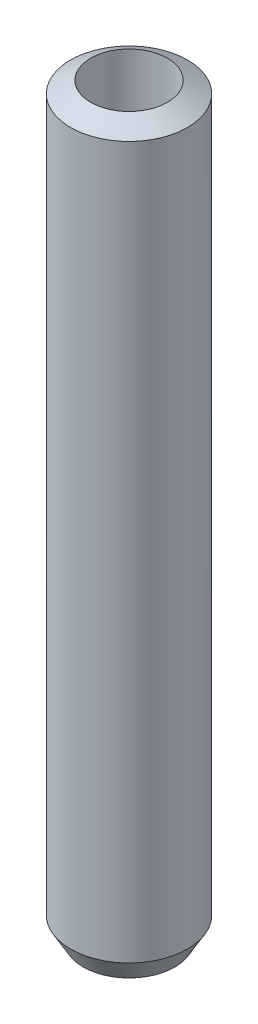
SolidWorks part; units mm, degrees
ref_plane "Front Plane" through (0, 0, 0) normal (0, 0, 1) x (1, 0, 0)
ref_plane "Top Plane" through (0, 0, 0) normal (0, 1, 0) x (1, 0, 0)
ref_plane "Right Plane" through (0, 0, 0) normal (1, 0, 0) x (0, 0, -1)
sketch "Sketch1" plane through (0, 0, 0) normal (0, 1, 0) x (1, 0, 0)
  circle A0 centre (0, 0) radius 17.5
  dimension "SHAFT_OD" = 35
extrude "Boss-Extrude1" add sketch "Sketch1" along normal blind 223.173
sketch "Sketch2" plane through (0, 0, 0) normal (0, 1, 0) x (1, 0, 0)
  circle A0 centre (0, 0) radius 11.4575
  dimension "BORE_D" = 22.9149
extrude "Cut-Extrude1" cut sketch "Sketch2" along normal through all
chamfer "Chamfer1" distance 3.7925 angle 60 2 edges at (0, 223.173, 17.5) (0, 0, 17.5) first distance on face at (0, 223.173, 17.5) first distance on face at (0, 0, 11.4575)
